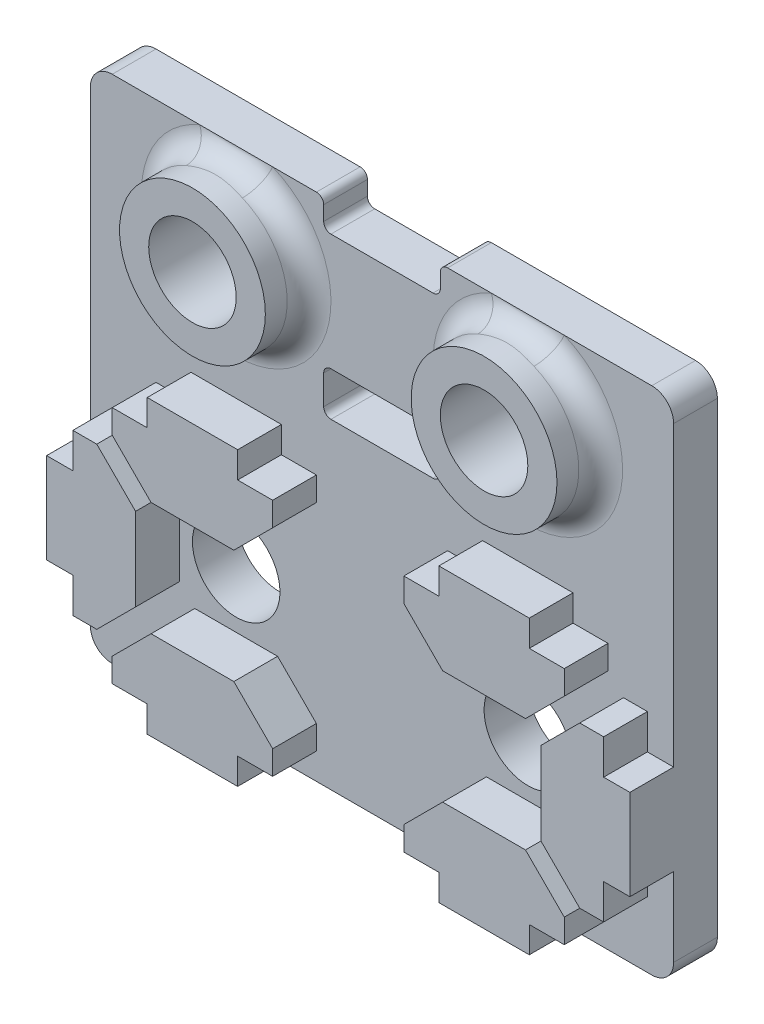
SolidWorks part; units mm, degrees
ref_plane "前视基准面" through (0, 0, 0) normal (0, 0, 1) x (1, 0, 0)
ref_plane "上视基准面" through (0, 0, 0) normal (0, 1, 0) x (1, 0, 0)
ref_plane "右视基准面" through (0, 0, 0) normal (1, 0, 0) x (0, 0, -1)
sketch "草图1" plane through (0, 0, 0) normal (0, 0, 1) x (1, 0, 0)
  line L1 (-20, -10) -> (20, -10)
  line L2 (-20, -10) -> (-20, 10)
  line L3 (-20, 10) -> (20, 10)
  line L4 (20, -10) -> (20, 10)
  line L5 (-20, -10) -> (20, 10) construction
  line L6 (-20, 10) -> (20, -10) construction
  point P0 (0, 0)
extrude "凸台-拉伸1" add sketch "草图1" along normal blind 3
sketch "草图2" plane through (0, 0, 3) normal (0, 0, 1) x (1, 0, 0)
  line L4 (-6.9, 8.2) -> (-6.9, 10)
  line L5 (-13.1, 8.2) -> (-13.1, 10)
  line L6 (-4.5, 6.5607) -> (-4.5, 8.2)
  line L7 (-4.5, 6.5607) -> (-7.1607, 3.9)
  line L9 (-16.5607, 5.5) -> (-18.2, 5.5)
  line L10 (-13.1, 8.2) -> (-15.5, 8.2)
  line L12 (-12.8393, -3.9) -> (-7.1607, -3.9)
  line L13 (-13.9, -2.8393) -> (-13.9, 2.8393)
  line L14 (-12.8393, 3.9) -> (-7.1607, 3.9)
  line L16 (-10, 3.9) -> (-10, -3.9) construction
  line L18 (-6.9, 8.2) -> (-4.5, 8.2)
  line L19 (-16.5607, 5.5) -> (-13.9, 2.8393)
  line L20 (-15.5, 6.5607) -> (-12.8393, 3.9)
  line L21 (-15.5, 6.5607) -> (-15.5, 8.2)
  line L22 (-18.2, 3.1) -> (-18.2, 5.5)
  line L23 (-18.2, 3.1) -> (-20, 3.1)
  line L24 (-18.2, -3.1) -> (-20, -3.1)
  line L25 (-18.2, -3.1) -> (-18.2, -5.5)
  line L26 (-15.5, -6.5607) -> (-15.5, -8.2)
  line L27 (-15.5, -6.5607) -> (-12.8393, -3.9)
  line L28 (-16.5607, -5.5) -> (-13.9, -2.8393)
  line L29 (-6.9, -8.2) -> (-4.5, -8.2)
  line L31 (-13.1, -8.2) -> (-15.5, -8.2)
  line L32 (-16.5607, -5.5) -> (-18.2, -5.5)
  line L34 (-4.5, -6.5607) -> (-7.1607, -3.9)
  line L35 (-4.5, -6.5607) -> (-4.5, -8.2)
  line L36 (-13.1, -8.2) -> (-13.1, -10)
  line L37 (-6.9, -8.2) -> (-6.9, -10)
  line L41 (18.2, 3.1) -> (20, 3.1)
  line L42 (13.1, 8.2) -> (13.1, 10)
  line L43 (6.9, 8.2) -> (6.9, 10)
  line L45 (18.2, 3.1) -> (18.2, 5.5)
  line L46 (15.5, 6.5607) -> (15.5, 8.2)
  line L47 (15.5, 6.5607) -> (12.8393, 3.9)
  line L48 (16.5607, 5.5) -> (13.9, 2.8393)
  line L49 (6.9, 8.2) -> (4.5, 8.2)
  line L51 (7.1607, -3.9) -> (12.8393, -3.9)
  line L53 (7.1607, 3.9) -> (12.8393, 3.9)
  line L54 (13.9, -2.8393) -> (13.9, 2.8393)
  line L55 (13.1, 8.2) -> (15.5, 8.2)
  line L56 (16.5607, 5.5) -> (18.2, 5.5)
  line L58 (4.5, 6.5607) -> (7.1607, 3.9)
  line L59 (4.5, 6.5607) -> (4.5, 8.2)
  line L60 (4.5, -6.5607) -> (4.5, -8.2)
  line L61 (4.5, -6.5607) -> (7.1607, -3.9)
  line L63 (16.5607, -5.5) -> (18.2, -5.5)
  line L64 (13.1, -8.2) -> (15.5, -8.2)
  line L66 (6.9, -8.2) -> (4.5, -8.2)
  line L67 (16.5607, -5.5) -> (13.9, -2.8393)
  line L68 (15.5, -6.5607) -> (12.8393, -3.9)
  line L69 (15.5, -6.5607) -> (15.5, -8.2)
  line L70 (18.2, -3.1) -> (18.2, -5.5)
  line L72 (6.9, -8.2) -> (6.9, -10)
  line L73 (13.1, -8.2) -> (13.1, -10)
  line L74 (18.2, -3.1) -> (20, -3.1)
  line L78 (10, 3.9) -> (10, -3.9) construction
  line L79 (6.1, 0) -> (13.9, 0) construction
  line L86 (13.1, 10) -> (6.9, 10)
  line L87 (20, 3.1) -> (20, -3.1)
  line L88 (13.1, -10) -> (6.9, -10)
  line L89 (-6.9, -10) -> (-13.1, -10)
  line L90 (-20, -3.1) -> (-20, 3.1)
  line L91 (-6.9, 10) -> (-13.1, 10)
  point P0 (-10, 0)
  point P8 (-10, 8.2)
  point P9 (-9.8043, 8.2)
  point P13 (-10, 8.2)
  point P20 (-5, 5)
  point P33 (-15, 5)
  point P50 (-15, -5)
  point P51 (-5, -5)
  point P52 (-10, -8.2)
  point P53 (-9.8043, -8.2)
  point P54 (10, 0)
  point P58 (10, 8.2)
  point P59 (10.1957, 8.2)
  point P63 (10, 8.2)
  point P70 (15, 5)
  point P83 (5, 5)
  point P102 (5, -5)
  point P103 (15, -5)
  point P104 (10, -8.2)
  point P105 (10.1957, -8.2)
extrude "凸台-拉伸2" add sketch "草图2" along normal blind 3
sketch "草图3" plane through (0, 0, 0) normal (0, 0, -1) x (-1, 0, 0)
  circle A0 centre (-10, 0) radius 3
  circle A1 centre (10, 0) radius 3
extrude "切除-拉伸1" cut sketch "草图3" against normal blind 3
sketch "草图4" plane through (0, 0, 0) normal (0, 0, -1) x (-1, 0, 0)
  line L0 (-20, 10) -> (20, 10)
  line L2 (-20, 10) -> (-20, 25)
  line L3 (-20, 25) -> (20, 25)
  line L4 (20, 10) -> (20, 25)
  circle A0 centre (-10, 19) radius 3
  circle A1 centre (10, 19) radius 3
extrude "凸台-拉伸3" add sketch "草图4" against normal blind 3
fillet "圆角3" radius 1.5 4 edges at (20, -10, 1.5) (-20, -10, 1.5) (20, 25, 1.5) (-20, 25, 1.5)
sketch "草图5" plane through (0, 0, 3) normal (0, 0, 1) x (1, 0, 0)
  circle A0 centre (-10, 19) radius 5
  circle A1 centre (10, 19) radius 5
  circle A2 centre (-10, 19) radius 3
  circle A3 centre (10, 19) radius 3
extrude "凸台-拉伸4" add sketch "草图5" along normal blind 3
fillet "圆角4" radius 1.5 2 edges at (5, 19, 3) (-15, 19, 3)
sketch "草图6" plane through (0, 0, 0) normal (0, 0, -1) x (-1, 0, 0)
  line L3 (0, 23.0058) -> (4, 23.0058)
  line L4 (4, 23.0058) -> (4, 25)
  line L5 (18.5, 25) -> (-18.5, 25) construction
  line L6 (4, 25) -> (-4, 25)
  line L7 (-4, 25) -> (-4, 23.0058)
  line L8 (-4, 23.0058) -> (0, 23.0058)
  line L10 (0, 15.0058) -> (-4, 15.0058)
  line L11 (-4, 15.0058) -> (-4, 12.0058)
  line L12 (-4, 12.0058) -> (4, 12.0058)
  line L13 (4, 12.0058) -> (4, 15.0058)
  line L14 (4, 15.0058) -> (0, 15.0058)
extrude "切除-拉伸2" cut sketch "草图6" against normal blind 10
fillet "圆角6" radius 0.5 8 edges at (4, 23.0058, 1.5) (-4, 23.0058, 1.5) (4, 25, 1.5) (-4, 25, 1.5) (4, 15.0058, 1.5) (4, 12.0058, 1.5) (-4, 12.0058, 1.5) (-4, 15.0058, 1.5)
